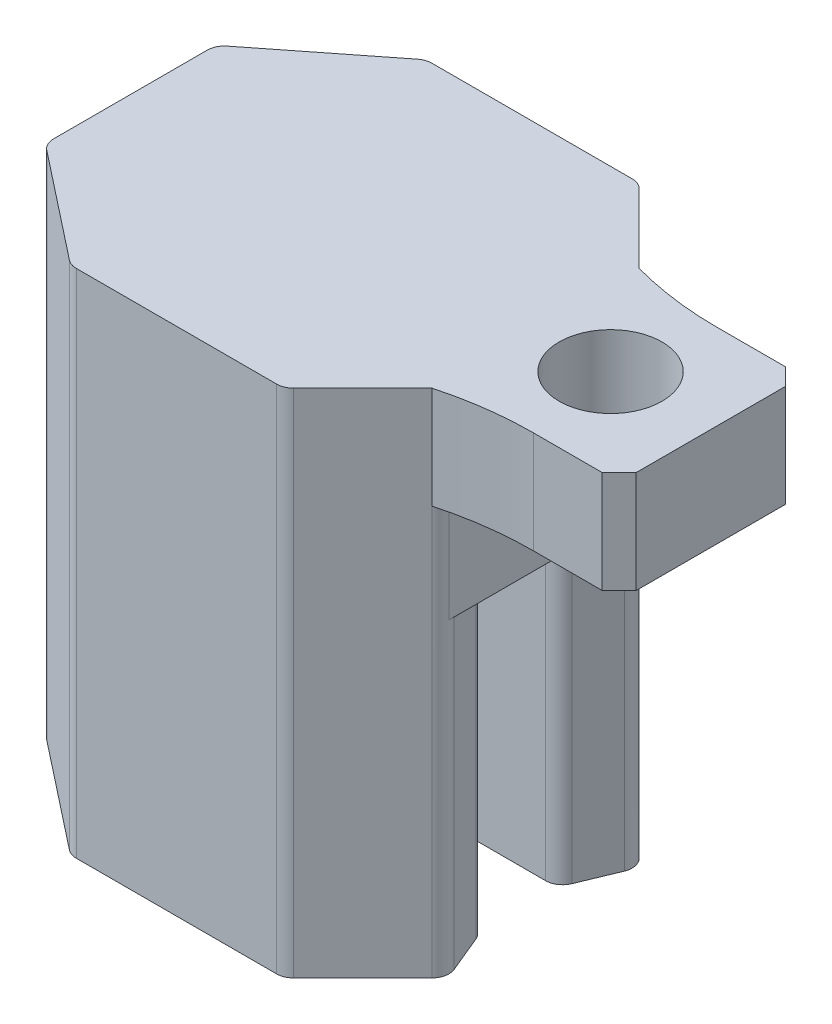
SolidWorks part; units mm, degrees
ref_plane "前视基准面" through (0, 0, 0) normal (0, 0, 1) x (1, 0, 0)
ref_plane "上视基准面" through (0, 0, 0) normal (0, 1, 0) x (1, 0, 0)
ref_plane "右视基准面" through (0, 0, 0) normal (1, 0, 0) x (0, 0, -1)
other "Configuration Table"
sketch "草图4" plane through (0, 0, 0) normal (0, 1, 0) x (1, 0, 0)
  line L0 (-2.7202, -7.5) -> (0.5103, -7.5) construction
  line L1 (1.9249, -6.9142) -> (6.0332, -2.8071) construction
  line L2 (5.3259, -1.1) -> (-3.0999, -1.1) construction
  line L3 (-5.3265, -1.1) -> (-3.0927, -1.1) construction
  line L4 (-3.0927, 1.1) -> (-5.3265, 1.1) construction
  line L5 (-3.0999, 1.1) -> (5.3259, 1.1) construction
  line L6 (6.0332, 2.8071) -> (1.9249, 6.9142) construction
  line L7 (0.5103, 7.5) -> (-2.7202, 7.5) construction
  line L8 (-5.3265, 1.1) -> (4.9919, 1.1)
  line L9 (-5.3265, 1.1) -> (-5.9898, 1.9483)
  line L10 (-5.9052, 2.6492) -> (-2.7762, 5.1125)
  line L11 (-2.467, 5.2196) -> (3.413, 5.2196)
  line L12 (3.7665, 5.0732) -> (5.7969, 3.0434)
  line L13 (5.9053, 2.4984) -> (5.4538, 1.4086)
  line L14 (-14.4979, 0) -> (14.4979, 0) construction
  line L15 (3.7665, -5.0732) -> (5.7969, -3.0434)
  line L16 (-2.467, -5.2196) -> (3.413, -5.2196)
  line L17 (-5.9052, -2.6492) -> (-2.7762, -5.1125)
  line L18 (-5.3265, -1.1) -> (-5.9898, -1.9483)
  line L19 (-5.3265, -1.1) -> (4.9919, -1.1)
  line L20 (5.9053, -2.4984) -> (5.4538, -1.4086)
  arc A0 (5.9053, 2.4984) -> (5.7969, 3.0434) centre (5.4434, 2.6898) ccw
  arc A1 (5.4538, 1.4086) -> (4.9919, 1.1) centre (4.9919, 1.6) cw
  arc A2 (3.7665, 5.0732) -> (3.413, 5.2196) centre (3.413, 4.7196) ccw
  arc A3 (-2.467, 5.2196) -> (-2.7762, 5.1125) centre (-2.467, 4.7196) ccw
  arc A4 (-5.9898, 1.9483) -> (-5.9052, 2.6492) centre (-5.5959, 2.2563) cw
  arc A5 (3.7665, -5.0732) -> (3.413, -5.2196) centre (3.413, -4.7196) cw
  arc A6 (-2.467, -5.2196) -> (-2.7762, -5.1125) centre (-2.467, -4.7196) cw
  arc A7 (-5.9898, -1.9483) -> (-5.9052, -2.6492) centre (-5.5959, -2.2563) ccw
  arc A8 (5.9053, -2.4984) -> (5.7969, -3.0434) centre (5.4434, -2.6898) cw
  arc A9 (5.4538, -1.4086) -> (4.9919, -1.1) centre (4.9919, -1.6) ccw
  ellipse E0 centre (-2.6402, 6.3612) end of major axis (-3.7821, 6.3612) minor radius 1.1416 (-2.7202, 7.5) -> (-3.0999, 7.4062) ccw construction
  ellipse E1 centre (-2.6412, -6.3611) end of major axis (-3.7831, -6.3611) minor radius 1.1416 (-3.0999, -7.4066) -> (-2.7202, -7.5) ccw construction
  ellipse E2 centre (-2.6342, -6.3611) end of major axis (-2.6342, -5.2195) minor radius 1.1413 (-3.4037, -7.2043) -> (-3.0927, -7.4066) ccw construction
  ellipse E3 centre (0.5103, -5.5) end of major axis (-1.4903, -5.5) minor radius 2 (0.5103, -7.5) -> (1.9249, -6.9142) ccw construction
  ellipse E4 centre (5.3259, -2.1) end of major axis (4.3256, -2.1) minor radius 1 (6.0332, -2.8071) -> (5.3259, -1.1) ccw construction
  ellipse E5 centre (-5.3265, -2.1) end of major axis (-5.3265, -1.1) minor radius 0.9997 (-5.3265, -1.1) -> (-6.2968, -2.3409) ccw construction
  ellipse E6 centre (3.1939, 0.0155) end of major axis (3.1939, 9.7971) minor radius 9.7787 (-6.2968, -2.3409) -> (-3.4037, -7.2043) ccw construction
  ellipse E7 centre (-5.3265, 2.1) end of major axis (-5.3265, 3.1) minor radius 0.9997 (-6.2968, 2.3409) -> (-5.3265, 1.1) ccw construction
  ellipse E8 centre (5.3259, 2.1) end of major axis (4.3256, 2.1) minor radius 1 (5.3259, 1.1) -> (6.0332, 2.8071) ccw construction
  ellipse E9 centre (0.5103, 5.5) end of major axis (2.5109, 5.5) minor radius 2 (1.9249, 6.9142) -> (0.5103, 7.5) ccw construction
  ellipse E10 centre (-2.6332, 6.3612) end of major axis (-2.6332, 7.5028) minor radius 1.1413 (-3.0927, 7.4062) -> (-3.4032, 7.2038) ccw construction
  ellipse E11 centre (3.1936, -0.0166) end of major axis (3.1936, 9.765) minor radius 9.7787 (-3.4032, 7.2038) -> (-6.2968, 2.3409) ccw construction
  point P90 (0, 0)
  point P99 (3.62, 5.2196)
  point P102 (-2.6402, 5.2196)
  dimension "D1" = 0.5
extrude "凸台-拉伸1" add sketch "草图4" along normal blind 9
sketch "草图5" plane through (0, 9, 0) normal (0, 1, 0) x (1, 0, 0)
  line L0 (3.7665, -5.0732) -> (5.7969, -3.0434) construction
  line L1 (-2.467, -5.2196) -> (3.413, -5.2196) construction
  line L2 (-5.9052, -2.6492) -> (-2.7762, -5.1125) construction
  line L3 (5.7969, 3.0434) -> (3.7665, 5.0732) construction
  line L4 (3.413, 5.2196) -> (-2.467, 5.2196) construction
  line L5 (-2.7762, 5.1125) -> (-5.9052, 2.6492) construction
  line L6 (3.7665, -5.0732) -> (5.7969, -3.0434)
  line L7 (-2.467, -5.2196) -> (3.413, -5.2196)
  line L8 (-5.9052, -2.6492) -> (-2.7762, -5.1125)
  line L9 (5.7969, 3.0434) -> (3.7665, 5.0732)
  line L10 (3.413, 5.2196) -> (-2.467, 5.2196)
  line L11 (-2.7762, 5.1125) -> (-5.9052, 2.6492)
  line L12 (-6.0959, 2.2563) -> (-6.0959, -2.2563)
  line L13 (5.9434, -2.6898) -> (5.9434, 2.6898)
  arc A0 (5.9053, 2.4984) -> (5.7969, 3.0434) centre (5.4434, 2.6898) ccw construction
  arc A1 (5.7969, -3.0434) -> (5.9053, -2.4984) centre (5.4434, -2.6898) ccw construction
  arc A2 (3.413, -5.2196) -> (3.7665, -5.0732) centre (3.413, -4.7196) ccw construction
  arc A3 (-2.7762, -5.1125) -> (-2.467, -5.2196) centre (-2.467, -4.7196) ccw construction
  arc A4 (-5.9898, -1.9483) -> (-5.9052, -2.6492) centre (-5.5959, -2.2563) ccw construction
  arc A5 (-5.9052, 2.6492) -> (-5.9898, 1.9483) centre (-5.5959, 2.2563) ccw construction
  arc A6 (3.7665, 5.0732) -> (3.413, 5.2196) centre (3.413, 4.7196) ccw construction
  arc A7 (-2.467, 5.2196) -> (-2.7762, 5.1125) centre (-2.467, 4.7196) ccw construction
  arc A8 (5.9434, 2.6898) -> (5.7969, 3.0434) centre (5.4434, 2.6898) ccw
  arc A9 (5.7969, -3.0434) -> (5.9434, -2.6898) centre (5.4434, -2.6898) ccw
  arc A10 (3.413, -5.2196) -> (3.7665, -5.0732) centre (3.413, -4.7196) ccw
  arc A11 (-2.7762, -5.1125) -> (-2.467, -5.2196) centre (-2.467, -4.7196) ccw
  arc A12 (-6.0959, -2.2563) -> (-5.9052, -2.6492) centre (-5.5959, -2.2563) ccw
  arc A13 (-5.9052, 2.6492) -> (-6.0959, 2.2563) centre (-5.5959, 2.2563) ccw
  arc A14 (3.7665, 5.0732) -> (3.413, 5.2196) centre (3.413, 4.7196) ccw
  arc A15 (-2.467, 5.2196) -> (-2.7762, 5.1125) centre (-2.467, 4.7196) ccw
extrude "凸台-拉伸2" add sketch "草图5" along normal blind 6
sketch "草图7" plane through (5.9434, 0, 0) normal (1, 0, 0) x (0, 0, -1)
  line L0 (-2.6898, 9) -> (2.6898, 9) construction
  line L1 (-2.6898, 12) -> (2.6898, 12)
  line L2 (-2.6898, 12) -> (-2.6898, 15)
  line L3 (-2.6898, 15) -> (2.6898, 15)
  line L4 (2.6898, 12) -> (2.6898, 15)
  line L5 (0, 15) -> (0, 12) construction
  line L6 (-2.6898, 13.5) -> (2.6898, 13.5) construction
  point P0 (0, 13.5)
  dimension "D1" = 3
  dimension "D2" = 3
extrude "凸台-拉伸3" add sketch "草图7" along normal blind 5
fillet "圆角1" radius 10 2 edges at (5.9434, 13.5, -2.6898) (5.9434, 13.5, 2.6898)
chamfer "倒角1" distance 0.5 angle 45 2 edges at (10.9434, 13.5, -2.6898) (10.9434, 13.5, 2.6898)
sketch "草图8" plane through (0, 15, 0) normal (0, 1, 0) x (1, 0, 0)
  circle A0 centre (8, 0) radius 1.51
  dimension "D1" = 8
extrude "切除-拉伸1" cut sketch "草图8" against normal up to surface (3 mm away) up to face at (8.3166, 12, 0)
